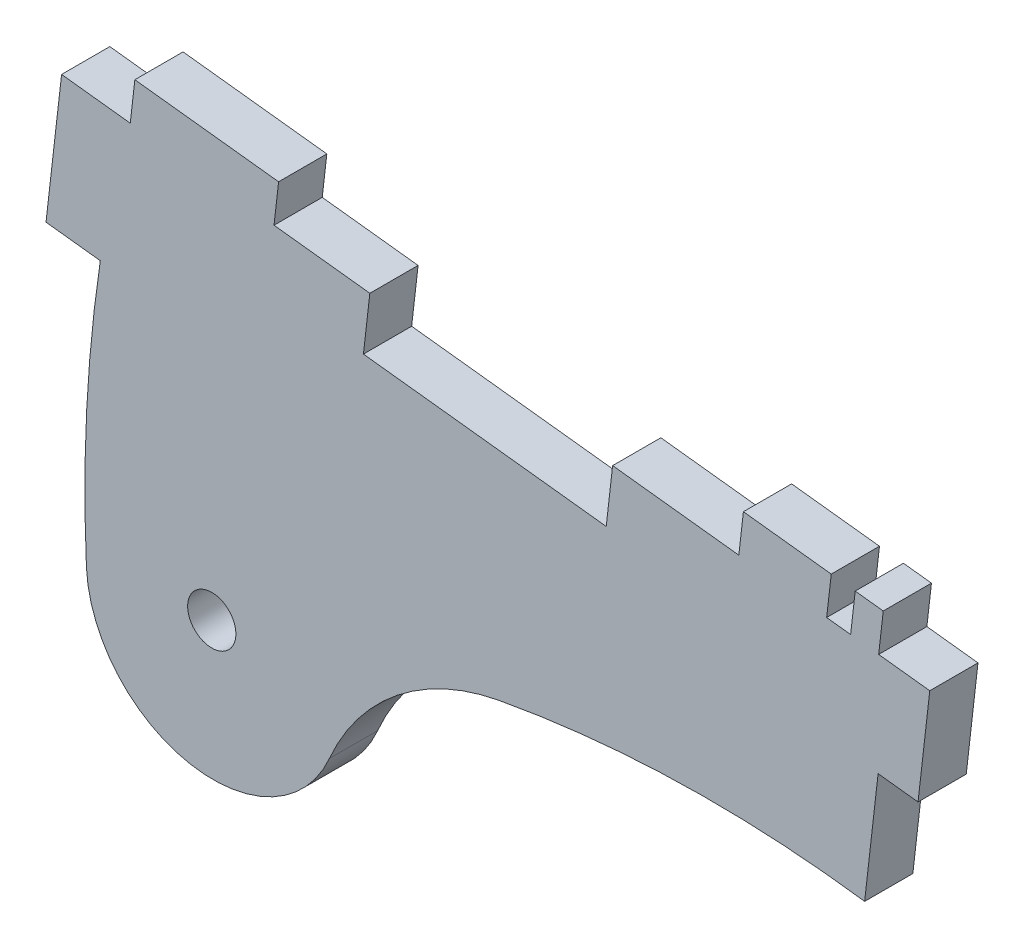
SolidWorks part; units mm, degrees
ref_plane "Plan de face" through (0, 0, 0) normal (0, 0, 1) x (1, 0, 0)
ref_plane "Plan de dessus" through (0, 0, 0) normal (0, 1, 0) x (1, 0, 0)
ref_plane "Plan de droite" through (0, 0, 0) normal (1, 0, 0) x (0, 0, -1)
sketch "Esquisse1" plane through (0, 0, 0) normal (0, 0, 1) x (1, 0, 0)
  line L0 (1154.0541, 1978.5248) -> (1207.7488, 1972.7911) construction
  line L1 (1154.1703, 1982.4517) -> (1153.2013, 1974.0071)
  line L2 (1153.2013, 1974.0071) -> (1156.5791, 1973.6195)
  line L3 (1154.1703, 1982.4517) -> (1158.4423, 1981.9615)
  line L4 (1158.4423, 1981.9615) -> (1158.7273, 1984.4452)
  line L5 (1158.7273, 1984.4452) -> (1167.6686, 1983.4191)
  line L6 (1167.6686, 1983.4191) -> (1167.3836, 1980.9354)
  line L7 (1167.3836, 1980.9354) -> (1173.3445, 1980.2514)
  line L8 (1173.3445, 1980.2514) -> (1172.9454, 1976.7742)
  line L9 (1172.9454, 1976.7742) -> (1188.0463, 1975.0413)
  line L10 (1188.0463, 1975.0413) -> (1188.4454, 1978.5185)
  line L11 (1188.4454, 1978.5185) -> (1196.2939, 1977.6179)
  line L12 (1196.2939, 1977.6179) -> (1196.5789, 1980.1016)
  line L13 (1196.5789, 1980.1016) -> (1202.043, 1979.4745)
  line L14 (1202.043, 1979.4745) -> (1201.758, 1976.9908)
  line L15 (1201.758, 1976.9908) -> (1203.2482, 1976.8198)
  line L16 (1203.2482, 1976.8198) -> (1203.5332, 1979.3035)
  line L17 (1203.5332, 1979.3035) -> (1205.2769, 1979.1034)
  line L18 (1205.2769, 1979.1034) -> (1204.9919, 1976.6197)
  line L19 (1204.9919, 1976.6197) -> (1208.171, 1976.2549)
  line L20 (1208.171, 1976.2549) -> (1207.4414, 1969.8966)
  line L21 (1207.4414, 1969.8966) -> (1204.9577, 1970.1816)
  line L22 (1204.9577, 1970.1816) -> (1204.1197, 1962.8796)
  circle A0 centre (1163.5123, 1957.7255) radius 1.5
  arc A2 (1155.7156, 1956.6882) -> (1170.8274, 1953.9314) centre (1163.5908, 1957.0598) ccw
  arc A3 (1156.5791, 1973.6195) -> (1155.7156, 1956.6882) centre (1242.1539, 1960.7677) ccw
  arc A4 (1170.8274, 1953.9314) -> (1181.3794, 1962.3372) centre (1183.9814, 1948.2449) cw
  arc A5 (1181.3794, 1962.3372) -> (1204.1197, 1962.8796) centre (1194.4435, 1891.5808) cw
  dimension "D45" = 3
  dimension "D46" = 24.5
  dimension "D1" = 54
  dimension "D2" = 4.3
  dimension "D3" = 8.5
  dimension "D4" = 90
  dimension "D5" = 90
  dimension "D6" = 3.4
  dimension "D7" = 90
  dimension "D8" = 90
  dimension "D9" = 90
  dimension "D10" = 90
  dimension "D11" = 90
  dimension "D12" = 90
  dimension "D13" = 90
  dimension "D14" = 90
  dimension "D15" = 90
  dimension "D16" = 90
  dimension "D17" = 90
  dimension "D18" = 90
  dimension "D19" = 90
  dimension "D20" = 90
  dimension "D21" = 90
  dimension "D22" = 90
  dimension "D23" = 90
  dimension "D24" = 90
  dimension "D25" = 90
  dimension "D26" = 2.5
  dimension "D27" = 9
  dimension "D28" = 2.5
  dimension "D29" = 6
  dimension "D30" = 3.5
  dimension "D31" = 15.2
  dimension "D32" = 3.5
  dimension "D33" = 7.9
  dimension "D34" = 2.5
  dimension "D35" = 5.5
  dimension "D36" = 1.5
  dimension "D37" = 2.5
  dimension "D38" = 2.5
  dimension "D39" = 1.5
  dimension "D40" = 2.5
  dimension "D41" = 3.2
  dimension "D42" = 6.4
  dimension "D43" = 2.5
  dimension "D44" = 7.35
  dimension "D47" = 12.1
base flange "Tôle de base pliée1" sketch "Esquisse1" thickness 3 reverse thickness direction no parameters "D1"=1.5
sketch "Lignes de pliage1" [suppressed] plane through (0, 0, 0) normal (0, 1, 0) x (1, 0, 0)
sketch "Cube de visualisation1" [suppressed] plane through (0, 0, 0) normal (0, 1, 0) x (1, 0, 0)
sheet metal parameters "Tôlerie1" thickness 3 parameters "D1"=1.5
flat pattern "Etat déplié1" [suppressed]
sketch "Lignes de pliage2" plane through (0, 0, 0) normal (0, 1, 0) x (1, 0, 0)
sketch3d "Cube de visualisation2" [suppressed]
  line L0 (-39.9882, 93.3546, 0) -> (14.0125, 87.1578, 0) construction
  line L1 (-43.9256, 59.0436, 0) -> (10.0752, 52.8468, 0) construction
  line L2 (-39.9882, 93.3546, 0) -> (-43.9256, 59.0436, 0) construction
  line L3 (14.0125, 87.1578, 0) -> (10.0752, 52.8468, 0) construction
